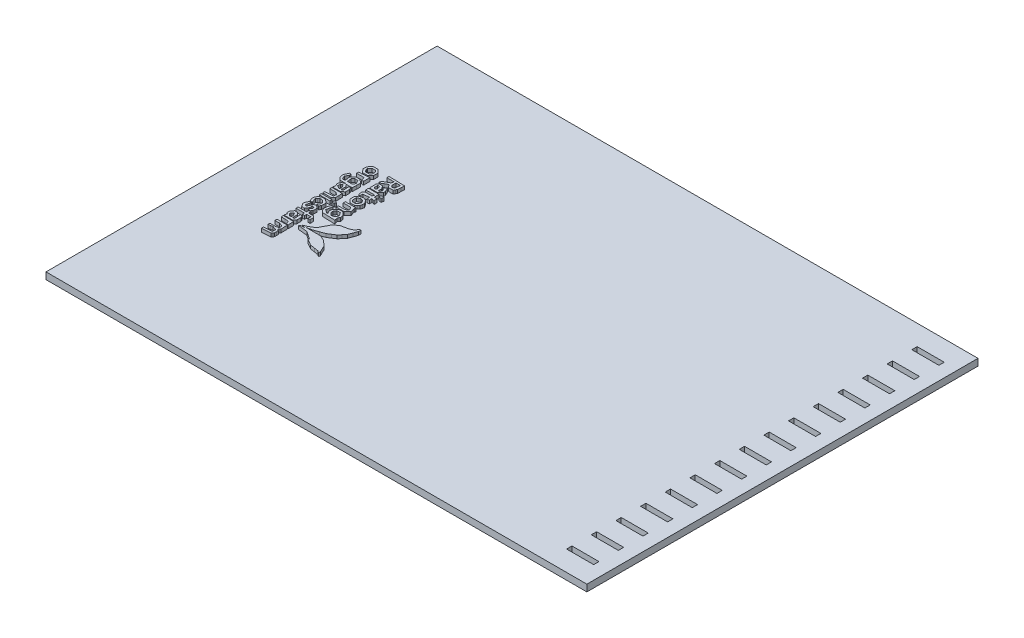
SolidWorks part; units mm, degrees
material "ABS"
ref_plane "Front Plane" through (0, 0, 0) normal (0, 0, 1) x (1, 0, 0)
ref_plane "Top Plane" through (0, 0, 0) normal (0, 1, 0) x (1, 0, 0)
ref_plane "Right Plane" through (0, 0, 0) normal (1, 0, 0) x (0, 0, -1)
sketch "Sketch1" plane through (0, 0, 0) normal (0, 1, 0) x (1, 0, 0)
  line L1 (-66.3921, 26.4776) -> (136.8079, 26.4776)
  line L2 (-66.3921, 26.4776) -> (-66.3921, -120.4614)
  line L3 (-66.3921, -120.4614) -> (136.8079, -120.4614)
  line L4 (136.8079, 26.4776) -> (136.8079, -120.4614)
  dimension "D1" = 203.2
  dimension "D2" = 146.939
extrude "Boss-Extrude1" add sketch "Sketch1" along normal blind 2.54
sketch "Sketch2" plane through (0, 2.54, 0) normal (0, 1, 0) x (0, 0, -1)
  line L14 (-120.4614, 66.3921) -> (-120.4614, -136.8079) construction
  line L15 (-110.8414, -131.7279) -> (-112.8414, -131.7279)
  line L16 (-110.8414, -131.7279) -> (-110.8414, -121.5679)
  line L17 (-110.8414, -121.5679) -> (-112.8414, -121.5679)
  line L18 (-112.8414, -131.7279) -> (-112.8414, -121.5679)
  line L19 (-120.4614, -136.8079) -> (26.4776, -136.8079) construction
  dimension "D1" = 2
  dimension "D2" = 7.62
  dimension "D3" = 5.08
  dimension "D4" = 10.16
extrude "Cut-Extrude1" cut sketch "Sketch2" against normal blind 2.794
pattern_linear "LPattern1" count 15 spacing 9.2642 along (0, 0, -1) of "Cut-Extrude1"
sketch "Sketch6" plane through (0, 2.54, 0) normal (0, 1, 0) x (1, 0, 0)
  line L8 (-40.8388, -35.001) -> (-40.6941, -35.6624)
  line L9 (-40.6941, -35.6624) -> (-40.2044, -36.1615)
  line L10 (-40.2044, -36.1615) -> (-39.7146, -36.6606)
  line L11 (-39.7146, -36.6606) -> (-38.5681, -36.6606)
  line L12 (-38.5681, -36.6606) -> (-37.4215, -36.6606)
  line L13 (-37.4215, -36.6606) -> (-37.9989, -36.8742)
  line L14 (-37.9989, -36.8742) -> (-38.5762, -37.0878)
  line L15 (-38.5762, -37.0878) -> (-38.8728, -37.6419)
  line L16 (-38.8728, -37.6419) -> (-39.1693, -38.1959)
  line L17 (-39.1693, -38.1959) -> (-38.9717, -38.7813)
  line L18 (-38.9717, -38.7813) -> (-38.774, -39.3666)
  line L19 (-38.774, -39.3666) -> (-38.8413, -39.8296)
  line L20 (-38.8413, -39.8296) -> (-38.9087, -40.2926)
  line L21 (-38.9087, -40.2926) -> (-37.4957, -40.2926)
  line L22 (-37.4957, -40.2926) -> (-36.0827, -40.2926)
  line L23 (-36.0827, -40.2926) -> (-35.4947, -39.8807)
  line L24 (-35.4947, -39.8807) -> (-34.9067, -39.4689)
  line L25 (-34.9067, -39.4689) -> (-34.9067, -38.7118)
  line L26 (-34.9067, -38.7118) -> (-34.9067, -37.9547)
  line L27 (-34.9067, -37.9547) -> (-35.0673, -37.5362)
  line L28 (-35.0673, -37.5362) -> (-35.2279, -37.1176)
  line L29 (-35.2279, -37.1176) -> (-35.5804, -37.1176)
  line L30 (-35.5804, -37.1176) -> (-35.9329, -37.1176)
  line L31 (-35.9329, -37.1176) -> (-35.8828, -38.2136)
  line L32 (-35.8828, -38.2136) -> (-35.8327, -39.3097)
  line L33 (-35.8327, -39.3097) -> (-36.1634, -39.4263)
  line L34 (-36.1634, -39.4263) -> (-36.4942, -39.543)
  line L35 (-36.4942, -39.543) -> (-36.4942, -38.6138)
  line L36 (-36.4942, -38.6138) -> (-36.4942, -37.6846)
  line L37 (-36.4942, -37.6846) -> (-36.9099, -37.2688)
  line L38 (-36.9099, -37.2688) -> (-37.3257, -36.853)
  line L39 (-37.3257, -36.853) -> (-36.1446, -36.853)
  line L40 (-36.1446, -36.853) -> (-34.9635, -36.853)
  line L41 (-34.9635, -36.853) -> (-34.9414, -35.2798)
  line L42 (-34.9414, -35.2798) -> (-34.9193, -33.7065)
  line L43 (-34.9193, -33.7065) -> (-35.6101, -33.1631)
  line L44 (-35.6101, -33.1631) -> (-36.301, -32.6197)
  line L45 (-36.301, -32.6197) -> (-37.0129, -32.6197)
  line L46 (-37.0129, -32.6197) -> (-37.7249, -32.6197)
  line L47 (-37.7249, -32.6197) -> (-38.331, -33.2649)
  line L48 (-38.331, -33.2649) -> (-38.9371, -33.9101)
  line L49 (-38.9371, -33.9101) -> (-38.8271, -34.8524)
  line L50 (-38.8271, -34.8524) -> (-38.7171, -35.7947)
  line L51 (-38.7171, -35.7947) -> (-39.1988, -35.7947)
  line L52 (-39.1988, -35.7947) -> (-39.6805, -35.7947)
  line L53 (-39.6805, -35.7947) -> (-39.977, -35.1441)
  line L54 (-39.977, -35.1441) -> (-40.2734, -34.4935)
  line L55 (-40.2734, -34.4935) -> (-39.8801, -33.8873)
  line L56 (-39.8801, -33.8873) -> (-39.4868, -33.2812)
  line L57 (-39.4868, -33.2812) -> (-39.6, -32.9504)
  line L58 (-39.6, -32.9504) -> (-39.7133, -32.6197)
  line L59 (-39.7133, -32.6197) -> (-39.9686, -32.6197)
  line L60 (-39.9686, -32.6197) -> (-40.2239, -32.6197)
  line L61 (-40.2239, -32.6197) -> (-40.6036, -33.4796)
  line L62 (-40.6036, -33.4796) -> (-40.9834, -34.3395)
  line L63 (-40.9834, -34.3395) -> (-40.8388, -35.001)
  line L64 (-38.3463, -38.4468) -> (-38.3463, -37.9426)
  line L65 (-38.3463, -37.9426) -> (-38.0415, -37.7543)
  line L66 (-38.0415, -37.7543) -> (-37.7368, -37.5659)
  line L67 (-37.7368, -37.5659) -> (-37.3801, -38.0538)
  line L68 (-37.3801, -38.0538) -> (-37.0233, -38.5417)
  line L69 (-37.0233, -38.5417) -> (-37.0233, -39.0203)
  line L70 (-37.0233, -39.0203) -> (-37.0233, -39.4989)
  line L71 (-37.0233, -39.4989) -> (-37.173, -39.4989)
  line L72 (-37.173, -39.4989) -> (-37.3227, -39.4989)
  line L73 (-37.3227, -39.4989) -> (-37.8345, -39.225)
  line L74 (-37.8345, -39.225) -> (-38.3463, -38.9511)
  line L75 (-38.3463, -38.9511) -> (-38.3463, -38.4468)
  line L76 (-38.0274, -34.8674) -> (-38.1055, -34.0723)
  line L77 (-38.1055, -34.0723) -> (-37.7761, -33.7429)
  line L78 (-37.7761, -33.7429) -> (-37.4467, -33.4135)
  line L79 (-37.4467, -33.4135) -> (-36.8324, -33.4135)
  line L80 (-36.8324, -33.4135) -> (-36.2183, -33.4135)
  line L81 (-36.2183, -33.4135) -> (-35.9075, -34.0955)
  line L82 (-35.9075, -34.0955) -> (-35.5968, -34.7775)
  line L83 (-35.5968, -34.7775) -> (-35.8759, -35.22)
  line L84 (-35.8759, -35.22) -> (-36.155, -35.6624)
  line L85 (-36.155, -35.6624) -> (-37.0522, -35.6624)
  line L86 (-37.0522, -35.6624) -> (-37.9494, -35.6624)
  line L87 (-37.9494, -35.6624) -> (-38.0274, -34.8674)
  line L88 (-39.1191, -28.1522) -> (-39.14, -28.5796)
  line L89 (-39.14, -28.5796) -> (-38.5916, -29.2767)
  line L90 (-38.5916, -29.2767) -> (-38.0433, -29.9739)
  line L91 (-38.0433, -29.9739) -> (-37.0041, -29.9739)
  line L92 (-37.0041, -29.9739) -> (-35.965, -29.9739)
  line L93 (-35.965, -29.9739) -> (-35.4358, -29.4447)
  line L94 (-35.4358, -29.4447) -> (-34.9067, -28.9155)
  line L95 (-34.9067, -28.9155) -> (-34.9067, -28.0727)
  line L96 (-34.9067, -28.0727) -> (-34.9067, -27.2298)
  line L97 (-34.9067, -27.2298) -> (-35.482, -26.6175)
  line L98 (-35.482, -26.6175) -> (-36.0572, -26.0051)
  line L99 (-36.0572, -26.0051) -> (-37.0285, -26.0051)
  line L100 (-37.0285, -26.0051) -> (-37.9997, -26.0051)
  line L101 (-37.9997, -26.0051) -> (-38.403, -26.4682)
  line L102 (-38.403, -26.4682) -> (-38.8064, -26.9312)
  line L103 (-38.8064, -26.9312) -> (-38.9523, -27.328)
  line L104 (-38.9523, -27.328) -> (-39.0982, -27.7249)
  line L105 (-39.0982, -27.7249) -> (-39.1191, -28.1522)
  line L106 (-38.3463, -27.8935) -> (-38.3463, -27.6304)
  line L107 (-38.3463, -27.6304) -> (-37.9305, -27.2147)
  line L108 (-37.9305, -27.2147) -> (-37.5147, -26.7989)
  line L109 (-37.5147, -26.7989) -> (-36.9251, -26.7989)
  line L110 (-36.9251, -26.7989) -> (-36.3354, -26.7989)
  line L111 (-36.3354, -26.7989) -> (-36.0179, -27.1164)
  line L112 (-36.0179, -27.1164) -> (-35.7004, -27.4339)
  line L113 (-35.7004, -27.4339) -> (-35.7004, -27.9895)
  line L114 (-35.7004, -27.9895) -> (-35.7004, -28.5451)
  line L115 (-35.7004, -28.5451) -> (-36.0179, -28.8626)
  line L116 (-36.0179, -28.8626) -> (-36.3354, -29.1801)
  line L117 (-36.3354, -29.1801) -> (-37.0669, -29.1801)
  line L118 (-37.0669, -29.1801) -> (-37.7985, -29.1801)
  line L119 (-37.7985, -29.1801) -> (-38.0724, -28.6684)
  line L120 (-38.0724, -28.6684) -> (-38.3463, -28.1566)
  line L121 (-38.3463, -28.1566) -> (-38.3463, -27.8935)
  line L122 (-39.1232, -47.6522) -> (-39.14, -48.0003)
  line L123 (-39.14, -48.0003) -> (-38.8661, -48.5121)
  line L124 (-38.8661, -48.5121) -> (-38.5922, -49.0239)
  line L125 (-38.5922, -49.0239) -> (-38.1764, -49.0239)
  line L126 (-38.1764, -49.0239) -> (-37.7605, -49.0239)
  line L127 (-37.7605, -49.0239) -> (-37.9511, -48.5609)
  line L128 (-37.9511, -48.5609) -> (-38.1417, -48.0978)
  line L129 (-38.1417, -48.0978) -> (-38.2645, -47.6743)
  line L130 (-38.2645, -47.6743) -> (-38.3873, -47.2507)
  line L131 (-38.3873, -47.2507) -> (-37.951, -46.8144)
  line L132 (-37.951, -46.8144) -> (-37.5147, -46.378)
  line L133 (-37.5147, -46.378) -> (-37.0233, -46.378)
  line L134 (-37.0233, -46.378) -> (-36.532, -46.378)
  line L135 (-36.532, -46.378) -> (-36.1162, -46.7938)
  line L136 (-36.1162, -46.7938) -> (-35.7004, -47.2096)
  line L137 (-35.7004, -47.2096) -> (-35.7004, -47.6669)
  line L138 (-35.7004, -47.6669) -> (-35.7004, -48.1243)
  line L139 (-35.7004, -48.1243) -> (-36.0093, -48.4331)
  line L140 (-36.0093, -48.4331) -> (-36.3181, -48.7419)
  line L141 (-36.3181, -48.7419) -> (-35.8503, -48.9215)
  line L142 (-35.8503, -48.9215) -> (-35.3824, -49.101)
  line L143 (-35.3824, -49.101) -> (-35.1486, -48.7317)
  line L144 (-35.1486, -48.7317) -> (-34.9148, -48.3624)
  line L145 (-34.9148, -48.3624) -> (-34.9107, -47.5217)
  line L146 (-34.9107, -47.5217) -> (-34.9067, -46.681)
  line L147 (-34.9067, -46.681) -> (-35.6038, -46.1327)
  line L148 (-35.6038, -46.1327) -> (-36.301, -45.5843)
  line L149 (-36.301, -45.5843) -> (-36.9441, -45.5843)
  line L150 (-36.9441, -45.5843) -> (-37.5873, -45.5843)
  line L151 (-37.5873, -45.5843) -> (-38.114, -45.8662)
  line L152 (-38.114, -45.8662) -> (-38.6407, -46.148)
  line L153 (-38.6407, -46.148) -> (-38.8736, -46.7261)
  line L154 (-38.8736, -46.7261) -> (-39.1065, -47.3041)
  line L155 (-39.1065, -47.3041) -> (-39.1232, -47.6522)
  line L156 (-39.1221, -50.8832) -> (-39.1401, -51.2874)
  line L157 (-39.1401, -51.2874) -> (-38.7282, -51.8754)
  line L158 (-38.7282, -51.8754) -> (-38.3162, -52.4635)
  line L159 (-38.3162, -52.4635) -> (-37.8171, -52.4635)
  line L160 (-37.8171, -52.4635) -> (-37.3179, -52.4635)
  line L161 (-37.3179, -52.4635) -> (-36.9061, -51.8754)
  line L162 (-36.9061, -51.8754) -> (-36.4942, -51.2874)
  line L163 (-36.4942, -51.2874) -> (-36.4942, -50.8171)
  line L164 (-36.4942, -50.8171) -> (-36.4942, -50.3468)
  line L165 (-36.4942, -50.3468) -> (-36.0973, -50.3468)
  line L166 (-36.0973, -50.3468) -> (-35.7004, -50.3468)
  line L167 (-35.7004, -50.3468) -> (-35.7004, -50.728)
  line L168 (-35.7004, -50.728) -> (-35.7004, -51.1093)
  line L169 (-35.7004, -51.1093) -> (-35.965, -51.2728)
  line L170 (-35.965, -51.2728) -> (-36.2296, -51.4364)
  line L171 (-36.2296, -51.4364) -> (-36.2296, -51.6936)
  line L172 (-36.2296, -51.6936) -> (-36.2296, -51.9509)
  line L173 (-36.2296, -51.9509) -> (-35.806, -52.1134)
  line L174 (-35.806, -52.1134) -> (-35.3824, -52.276)
  line L175 (-35.3824, -52.276) -> (-35.1486, -51.9067)
  line L176 (-35.1486, -51.9067) -> (-34.9148, -51.5374)
  line L177 (-34.9148, -51.5374) -> (-34.9107, -50.8508)
  line L178 (-34.9107, -50.8508) -> (-34.9067, -50.1642)
  line L179 (-34.9067, -50.1642) -> (-35.426, -49.6942)
  line L180 (-35.426, -49.6942) -> (-35.9453, -49.2243)
  line L181 (-35.9453, -49.2243) -> (-36.364, -49.3849)
  line L182 (-36.364, -49.3849) -> (-36.7827, -49.5456)
  line L183 (-36.7827, -49.5456) -> (-37.1788, -50.4937)
  line L184 (-37.1788, -50.4937) -> (-37.5749, -51.4418)
  line L185 (-37.5749, -51.4418) -> (-37.8944, -51.3288)
  line L186 (-37.8944, -51.3288) -> (-38.214, -51.2159)
  line L187 (-38.214, -51.2159) -> (-38.1648, -50.8475)
  line L188 (-38.1648, -50.8475) -> (-38.1156, -50.4791)
  line L189 (-38.1156, -50.4791) -> (-37.9355, -49.8838)
  line L190 (-37.9355, -49.8838) -> (-37.7554, -49.2885)
  line L191 (-37.7554, -49.2885) -> (-38.1427, -49.2885)
  line L192 (-38.1427, -49.2885) -> (-38.53, -49.2885)
  line L193 (-38.53, -49.2885) -> (-38.8171, -49.8838)
  line L194 (-38.8171, -49.8838) -> (-39.1042, -50.4791)
  line L195 (-39.1042, -50.4791) -> (-39.1221, -50.8832)
  line L196 (-39.1401, -56.7401) -> (-39.1401, -57.1947)
  line L197 (-39.1401, -57.1947) -> (-38.9003, -57.3429)
  line L198 (-38.9003, -57.3429) -> (-38.6606, -57.4911)
  line L199 (-38.6606, -57.4911) -> (-38.7989, -58.02)
  line L200 (-38.7989, -58.02) -> (-38.9372, -58.5489)
  line L201 (-38.9372, -58.5489) -> (-37.3378, -58.5489)
  line L202 (-37.3378, -58.5489) -> (-35.7383, -58.5489)
  line L203 (-35.7383, -58.5489) -> (-35.3225, -58.1331)
  line L204 (-35.3225, -58.1331) -> (-34.9067, -57.7173)
  line L205 (-34.9067, -57.7173) -> (-34.9067, -56.9641)
  line L206 (-34.9067, -56.9641) -> (-34.9067, -56.2109)
  line L207 (-34.9067, -56.2109) -> (-35.0674, -55.7924)
  line L208 (-35.0674, -55.7924) -> (-35.228, -55.3739)
  line L209 (-35.228, -55.3739) -> (-35.6013, -55.3739)
  line L210 (-35.6013, -55.3739) -> (-35.9747, -55.3739)
  line L211 (-35.9747, -55.3739) -> (-35.9037, -56.4698)
  line L212 (-35.9037, -56.4698) -> (-35.8328, -57.5658)
  line L213 (-35.8328, -57.5658) -> (-36.1635, -57.6825)
  line L214 (-36.1635, -57.6825) -> (-36.4942, -57.7992)
  line L215 (-36.4942, -57.7992) -> (-36.4942, -56.87)
  line L216 (-36.4942, -56.87) -> (-36.4942, -55.9408)
  line L217 (-36.4942, -55.9408) -> (-36.91, -55.5251)
  line L218 (-36.91, -55.5251) -> (-37.3258, -55.1093)
  line L219 (-37.3258, -55.1093) -> (-37.8211, -55.1093)
  line L220 (-37.8211, -55.1093) -> (-38.3163, -55.1093)
  line L221 (-38.3163, -55.1093) -> (-38.7282, -55.6973)
  line L222 (-38.7282, -55.6973) -> (-39.1401, -56.2854)
  line L223 (-39.1401, -56.2854) -> (-39.1401, -56.7401)
  line L224 (-38.3463, -56.8086) -> (-38.3463, -56.497)
  line L225 (-38.3463, -56.497) -> (-37.9679, -56.183)
  line L226 (-37.9679, -56.183) -> (-37.5895, -55.8689)
  line L227 (-37.5895, -55.8689) -> (-37.3065, -56.3977)
  line L228 (-37.3065, -56.3977) -> (-37.0234, -56.9266)
  line L229 (-37.0234, -56.9266) -> (-37.0234, -57.3409)
  line L230 (-37.0234, -57.3409) -> (-37.0234, -57.7551)
  line L231 (-37.0234, -57.7551) -> (-37.3674, -57.7551)
  line L232 (-37.3674, -57.7551) -> (-37.7113, -57.7551)
  line L233 (-37.7113, -57.7551) -> (-38.0288, -57.4376)
  line L234 (-38.0288, -57.4376) -> (-38.3463, -57.1201)
  line L235 (-38.3463, -57.1201) -> (-38.3463, -56.8086)
  line L236 (-38.8754, -30.8999) -> (-38.8754, -31.2968)
  line L237 (-38.8754, -31.2968) -> (-37.4253, -31.2968)
  line L238 (-37.4253, -31.2968) -> (-35.9751, -31.2968)
  line L239 (-35.9751, -31.2968) -> (-35.8091, -31.9583)
  line L240 (-35.8091, -31.9583) -> (-35.643, -32.6197)
  line L241 (-35.643, -32.6197) -> (-35.2845, -32.6197)
  line L242 (-35.2845, -32.6197) -> (-34.926, -32.6197)
  line L243 (-34.926, -32.6197) -> (-34.9505, -31.3963)
  line L244 (-34.9505, -31.3963) -> (-34.9751, -30.1728)
  line L245 (-34.9751, -30.1728) -> (-36.3299, -30.3357)
  line L246 (-36.3299, -30.3357) -> (-37.6848, -30.4984)
  line L247 (-37.6848, -30.4984) -> (-38.2801, -30.5008)
  line L248 (-38.2801, -30.5008) -> (-38.8754, -30.503)
  line L249 (-38.8754, -30.503) -> (-38.8754, -30.8999)
  line L250 (-38.8754, -40.9541) -> (-38.8754, -41.351)
  line L251 (-38.8754, -41.351) -> (-37.7354, -41.351)
  line L252 (-37.7354, -41.351) -> (-36.5953, -41.351)
  line L253 (-36.5953, -41.351) -> (-36.1191, -41.6992)
  line L254 (-36.1191, -41.6992) -> (-35.6429, -42.0474)
  line L255 (-35.6429, -42.0474) -> (-35.7404, -42.5591)
  line L256 (-35.7404, -42.5591) -> (-35.8379, -43.0708)
  line L257 (-35.8379, -43.0708) -> (-37.3566, -43.1501)
  line L258 (-37.3566, -43.1501) -> (-38.8754, -43.2295)
  line L259 (-38.8754, -43.2295) -> (-38.8754, -43.6131)
  line L260 (-38.8754, -43.6131) -> (-38.8754, -43.9968)
  line L261 (-38.8754, -43.9968) -> (-37.3068, -43.9968)
  line L262 (-37.3068, -43.9968) -> (-35.7382, -43.9968)
  line L263 (-35.7382, -43.9968) -> (-35.3275, -43.5861)
  line L264 (-35.3275, -43.5861) -> (-34.9168, -43.1754)
  line L265 (-34.9168, -43.1754) -> (-34.9463, -41.8663)
  line L266 (-34.9463, -41.8663) -> (-34.9758, -40.5572)
  line L267 (-34.9758, -40.5572) -> (-36.9256, -40.5572)
  line L268 (-36.9256, -40.5572) -> (-38.8754, -40.5572)
  line L269 (-38.8754, -40.5572) -> (-38.8754, -40.9541)
  line L270 (-38.8754, -44.9228) -> (-38.8754, -45.3197)
  line L271 (-38.8754, -45.3197) -> (-36.891, -45.3197)
  line L272 (-36.891, -45.3197) -> (-34.9067, -45.3197)
  line L273 (-34.9067, -45.3197) -> (-34.9067, -44.9228)
  line L274 (-34.9067, -44.9228) -> (-34.9067, -44.526)
  line L275 (-34.9067, -44.526) -> (-36.891, -44.526)
  line L276 (-36.891, -44.526) -> (-38.8754, -44.526)
  line L277 (-38.8754, -44.526) -> (-38.8754, -44.9228)
  line L278 (-38.8754, -53.6541) -> (-38.8754, -54.051)
  line L279 (-38.8754, -54.051) -> (-37.2879, -54.051)
  line L280 (-37.2879, -54.051) -> (-35.7004, -54.051)
  line L281 (-35.7004, -54.051) -> (-35.7004, -54.4478)
  line L282 (-35.7004, -54.4478) -> (-35.7004, -54.8447)
  line L283 (-35.7004, -54.8447) -> (-35.3035, -54.8447)
  line L284 (-35.3035, -54.8447) -> (-34.9067, -54.8447)
  line L285 (-34.9067, -54.8447) -> (-34.9067, -54.4478)
  line L286 (-34.9067, -54.4478) -> (-34.9067, -54.051)
  line L287 (-34.9067, -54.051) -> (-34.1129, -54.051)
  line L288 (-34.1129, -54.051) -> (-33.3192, -54.051)
  line L289 (-33.3192, -54.051) -> (-33.3192, -54.5801)
  line L290 (-33.3192, -54.5801) -> (-33.3192, -55.1093)
  line L291 (-33.3192, -55.1093) -> (-32.9223, -55.1093)
  line L292 (-32.9223, -55.1093) -> (-32.5254, -55.1093)
  line L293 (-32.5254, -55.1093) -> (-32.5254, -54.5008)
  line L294 (-32.5254, -54.5008) -> (-32.5254, -53.8922)
  line L295 (-32.5254, -53.8922) -> (-32.8429, -53.5747)
  line L296 (-32.8429, -53.5747) -> (-33.1604, -53.2572)
  line L297 (-33.1604, -53.2572) -> (-34.0335, -53.2572)
  line L298 (-34.0335, -53.2572) -> (-34.9067, -53.2572)
  line L299 (-34.9067, -53.2572) -> (-34.9067, -52.8603)
  line L300 (-34.9067, -52.8603) -> (-34.9067, -52.4635)
  line L301 (-34.9067, -52.4635) -> (-35.3035, -52.4635)
  line L302 (-35.3035, -52.4635) -> (-35.7004, -52.4635)
  line L303 (-35.7004, -52.4635) -> (-35.7004, -52.8603)
  line L304 (-35.7004, -52.8603) -> (-35.7004, -53.2572)
  line L305 (-35.7004, -53.2572) -> (-37.2879, -53.2572)
  line L306 (-37.2879, -53.2572) -> (-38.8754, -53.2572)
  line L307 (-38.8754, -53.2572) -> (-38.8754, -53.6541)
  line L308 (-38.8754, -59.1965) -> (-38.8754, -59.5796)
  line L309 (-38.8754, -59.5796) -> (-37.4863, -59.6595)
  line L310 (-37.4863, -59.6595) -> (-36.0973, -59.7395)
  line L311 (-36.0973, -59.7395) -> (-35.8361, -60.3348)
  line L312 (-35.8361, -60.3348) -> (-35.5749, -60.9301)
  line L313 (-35.5749, -60.9301) -> (-35.2574, -60.9301)
  line L314 (-35.2574, -60.9301) -> (-34.9398, -60.9301)
  line L315 (-34.9398, -60.9301) -> (-34.9544, -59.8718)
  line L316 (-34.9544, -59.8718) -> (-34.9691, -58.8135)
  line L317 (-34.9691, -58.8135) -> (-36.9222, -58.8135)
  line L318 (-36.9222, -58.8135) -> (-38.8754, -58.8135)
  line L319 (-38.8754, -58.8135) -> (-38.8754, -59.1965)
  line L320 (-38.8754, -61.5916) -> (-38.8754, -61.9885)
  line L321 (-38.8754, -61.9885) -> (-37.9666, -61.9885)
  line L322 (-37.9666, -61.9885) -> (-37.0578, -61.9885)
  line L323 (-37.0578, -61.9885) -> (-36.3791, -62.2465)
  line L324 (-36.3791, -62.2465) -> (-35.7004, -62.5045)
  line L325 (-35.7004, -62.5045) -> (-35.7004, -63.0094)
  line L326 (-35.7004, -63.0094) -> (-35.7004, -63.5143)
  line L327 (-35.7004, -63.5143) -> (-36.2957, -63.6738)
  line L328 (-36.2957, -63.6738) -> (-36.891, -63.8333)
  line L329 (-36.891, -63.8333) -> (-37.8832, -63.8369)
  line L330 (-37.8832, -63.8369) -> (-38.8754, -63.8406)
  line L331 (-38.8754, -63.8406) -> (-38.8754, -64.2208)
  line L332 (-38.8754, -64.2208) -> (-38.8754, -64.601)
  line L333 (-38.8754, -64.601) -> (-38.0155, -64.464)
  line L334 (-38.0155, -64.464) -> (-37.1556, -64.327)
  line L335 (-37.1556, -64.327) -> (-36.4097, -64.6134)
  line L336 (-36.4097, -64.6134) -> (-35.6637, -64.8997)
  line L337 (-35.6637, -64.8997) -> (-35.7482, -65.4946)
  line L338 (-35.7482, -65.4946) -> (-35.8327, -66.0895)
  line L339 (-35.8327, -66.0895) -> (-37.3541, -66.1689)
  line L340 (-37.3541, -66.1689) -> (-38.8754, -66.2482)
  line L341 (-38.8754, -66.2482) -> (-38.8754, -66.6627)
  line L342 (-38.8754, -66.6627) -> (-38.8754, -67.0772)
  line L343 (-38.8754, -67.0772) -> (-38.3374, -67.043)
  line L344 (-38.3374, -67.043) -> (-35.3996, -66.8559)
  line L345 (-35.3996, -66.8559) -> (-35.1572, -66.4727)
  line L346 (-35.1572, -66.4727) -> (-34.9148, -66.0895)
  line L347 (-34.9148, -66.0895) -> (-34.9107, -65.3775)
  line L348 (-34.9107, -65.3775) -> (-34.9067, -64.6655)
  line L349 (-34.9067, -64.6655) -> (-35.1841, -64.4941)
  line L350 (-35.1841, -64.4941) -> (-35.4615, -64.3226)
  line L351 (-35.4615, -64.3226) -> (-35.1928, -63.9988)
  line L352 (-35.1928, -63.9988) -> (-34.924, -63.6749)
  line L353 (-34.924, -63.6749) -> (-34.9489, -62.4348)
  line L354 (-34.9489, -62.4348) -> (-34.9738, -61.1947)
  line L355 (-34.9738, -61.1947) -> (-36.9246, -61.1947)
  line L356 (-36.9246, -61.1947) -> (-38.8754, -61.1947)
  line L357 (-38.8754, -61.1947) -> (-38.8754, -61.5916)
  line L358 (-34.1129, -44.9384) -> (-34.1129, -45.3197)
  line L359 (-34.1129, -45.3197) -> (-33.7317, -45.3197)
  line L360 (-33.7317, -45.3197) -> (-33.3504, -45.3197)
  line L361 (-33.3504, -45.3197) -> (-33.1686, -45.0255)
  line L362 (-33.1686, -45.0255) -> (-32.9868, -44.7314)
  line L363 (-32.9868, -44.7314) -> (-33.3388, -44.5138)
  line L364 (-33.3388, -44.5138) -> (-33.6908, -44.2963)
  line L365 (-33.6908, -44.2963) -> (-33.9018, -44.4267)
  line L366 (-33.9018, -44.4267) -> (-34.1129, -44.5572)
  line L367 (-34.1129, -44.5572) -> (-34.1129, -44.9384)
  line L368 (-33.5659, -48.3992) -> (-33.5838, -49.2298)
  line L369 (-33.5838, -49.2298) -> (-33.0782, -49.8545)
  line L370 (-33.0782, -49.8545) -> (-32.5725, -50.4791)
  line L371 (-32.5725, -50.4791) -> (-30.1296, -50.573)
  line L372 (-30.1296, -50.573) -> (-27.6867, -50.6669)
  line L373 (-27.6867, -50.6669) -> (-27.846, -50.0576)
  line L374 (-27.846, -50.0576) -> (-28.0054, -49.4483)
  line L375 (-28.0054, -49.4483) -> (-27.7223, -49.1072)
  line L376 (-27.7223, -49.1072) -> (-27.4392, -48.7662)
  line L377 (-27.4392, -48.7662) -> (-27.6043, -48.1086)
  line L378 (-27.6043, -48.1086) -> (-27.7693, -47.451)
  line L379 (-27.7693, -47.451) -> (-28.3452, -46.9145)
  line L380 (-28.3452, -46.9145) -> (-28.921, -46.378)
  line L381 (-28.921, -46.378) -> (-29.6769, -46.378)
  line L382 (-29.6769, -46.378) -> (-30.4328, -46.378)
  line L383 (-30.4328, -46.378) -> (-31.0822, -47.0275)
  line L384 (-31.0822, -47.0275) -> (-31.7317, -47.6769)
  line L385 (-31.7317, -47.6769) -> (-31.7317, -48.2355)
  line L386 (-31.7317, -48.2355) -> (-31.7317, -48.7941)
  line L387 (-31.7317, -48.7941) -> (-31.4578, -49.3059)
  line L388 (-31.4578, -49.3059) -> (-31.1839, -49.8176)
  line L389 (-31.1839, -49.8176) -> (-31.3989, -49.8176)
  line L390 (-31.3989, -49.8176) -> (-31.6139, -49.8176)
  line L391 (-31.6139, -49.8176) -> (-32.2272, -49.3881)
  line L392 (-32.2272, -49.3881) -> (-32.8405, -48.9585)
  line L393 (-32.8405, -48.9585) -> (-32.7016, -48.2636)
  line L394 (-32.7016, -48.2636) -> (-32.5628, -47.5687)
  line L395 (-32.5628, -47.5687) -> (-32.478, -47.068)
  line L396 (-32.478, -47.068) -> (-32.3931, -46.5673)
  line L397 (-32.3931, -46.5673) -> (-32.6801, -46.4652)
  line L398 (-32.6801, -46.4652) -> (-32.9671, -46.3631)
  line L399 (-32.9671, -46.3631) -> (-33.2575, -46.9659)
  line L400 (-33.2575, -46.9659) -> (-33.5479, -47.5687)
  line L401 (-33.5479, -47.5687) -> (-33.5659, -48.3992)
  line L402 (-30.9299, -48.5198) -> (-30.9218, -48.0978)
  line L403 (-30.9218, -48.0978) -> (-30.6521, -47.6348)
  line L404 (-30.6521, -47.6348) -> (-30.3825, -47.1718)
  line L405 (-30.3825, -47.1718) -> (-29.7403, -47.1718)
  line L406 (-29.7403, -47.1718) -> (-29.098, -47.1718)
  line L407 (-29.098, -47.1718) -> (-28.6763, -47.8155)
  line L408 (-28.6763, -47.8155) -> (-28.2545, -48.4592)
  line L409 (-28.2545, -48.4592) -> (-28.5376, -48.9882)
  line L410 (-28.5376, -48.9882) -> (-28.8207, -49.5172)
  line L411 (-28.8207, -49.5172) -> (-29.3691, -49.6913)
  line L412 (-29.3691, -49.6913) -> (-29.9175, -49.8653)
  line L413 (-29.9175, -49.8653) -> (-30.4277, -49.4036)
  line L414 (-30.4277, -49.4036) -> (-30.9379, -48.9419)
  line L415 (-30.9379, -48.9419) -> (-30.9299, -48.5198)
  line L416 (-31.0663, -59.3896) -> (-29.2954, -59.5688)
  line L417 (-29.2954, -59.5688) -> (-27.8677, -60.5168)
  line L418 (-27.8677, -60.5168) -> (-26.44, -61.4647)
  line L419 (-26.44, -61.4647) -> (-26.44, -61.7154)
  line L420 (-26.44, -61.7154) -> (-26.44, -61.9662)
  line L421 (-26.44, -61.9662) -> (-25.3155, -62.6236)
  line L422 (-25.3155, -62.6236) -> (-24.191, -63.281)
  line L423 (-24.191, -63.281) -> (-22.5109, -63.5503)
  line L424 (-22.5109, -63.5503) -> (-20.8309, -63.8197)
  line L425 (-20.8309, -63.8197) -> (-20.4604, -64.1271)
  line L426 (-20.4604, -64.1271) -> (-20.09, -64.4345)
  line L427 (-20.09, -64.4345) -> (-20.0926, -64.0714)
  line L428 (-20.0926, -64.0714) -> (-20.0952, -63.7083)
  line L429 (-20.0952, -63.7083) -> (-20.7172, -62.3853)
  line L430 (-20.7172, -62.3853) -> (-21.3393, -61.0624)
  line L431 (-21.3393, -61.0624) -> (-22.3165, -60.183)
  line L432 (-22.3165, -60.183) -> (-23.2938, -59.3036)
  line L433 (-23.2938, -59.3036) -> (-24.2716, -58.8762)
  line L434 (-24.2716, -58.8762) -> (-25.2494, -58.4487)
  line L435 (-25.2494, -58.4487) -> (-27.9705, -58.4327)
  line L436 (-27.9705, -58.4327) -> (-30.6916, -58.4166)
  line L437 (-30.6916, -58.4166) -> (-29.703, -58.2111)
  line L438 (-29.703, -58.2111) -> (-28.7143, -58.0057)
  line L439 (-28.7143, -58.0057) -> (-26.8496, -57.3346)
  line L440 (-26.8496, -57.3346) -> (-24.9848, -56.6634)
  line L441 (-24.9848, -56.6634) -> (-23.7214, -55.8545)
  line L442 (-23.7214, -55.8545) -> (-22.458, -55.0456)
  line L443 (-22.458, -55.0456) -> (-21.5701, -54.0083)
  line L444 (-21.5701, -54.0083) -> (-20.6822, -52.971)
  line L445 (-20.6822, -52.971) -> (-20.1215, -51.4333)
  line L446 (-20.1215, -51.4333) -> (-19.5608, -49.8956)
  line L447 (-19.5608, -49.8956) -> (-19.5608, -49.4597)
  line L448 (-19.5608, -49.4597) -> (-19.5608, -49.0239)
  line L449 (-19.5608, -49.0239) -> (-19.8161, -49.0239)
  line L450 (-19.8161, -49.0239) -> (-20.0714, -49.0239)
  line L451 (-20.0714, -49.0239) -> (-20.3531, -49.5503)
  line L452 (-20.3531, -49.5503) -> (-20.6349, -50.0767)
  line L453 (-20.6349, -50.0767) -> (-21.4209, -50.4832)
  line L454 (-21.4209, -50.4832) -> (-22.207, -50.8897)
  line L455 (-22.207, -50.8897) -> (-23.5726, -51.1487)
  line L456 (-23.5726, -51.1487) -> (-24.9382, -51.4077)
  line L457 (-24.9382, -51.4077) -> (-25.8091, -52.072)
  line L458 (-25.8091, -52.072) -> (-26.68, -52.7362)
  line L459 (-26.68, -52.7362) -> (-27.6648, -54.6102)
  line L460 (-27.6648, -54.6102) -> (-28.6495, -56.4842)
  line L461 (-28.6495, -56.4842) -> (-29.6743, -57.1311)
  line L462 (-29.6743, -57.1311) -> (-30.6991, -57.778)
  line L463 (-30.6991, -57.778) -> (-31.4138, -58.0683)
  line L464 (-31.4138, -58.0683) -> (-32.1285, -58.3585)
  line L465 (-32.1285, -58.3585) -> (-31.4671, -58.5596)
  line L466 (-31.4671, -58.5596) -> (-30.8056, -58.7607)
  line L467 (-30.8056, -58.7607) -> (-31.6214, -58.7871)
  line L468 (-31.6214, -58.7871) -> (-32.4372, -58.8135)
  line L469 (-32.4372, -58.8135) -> (-32.6372, -59.0119)
  line L470 (-32.6372, -59.0119) -> (-32.8371, -59.2104)
  line L471 (-32.8371, -59.2104) -> (-31.0663, -59.3896)
  line L472 (-31.7317, -26.6579) -> (-31.7317, -27.0635)
  line L473 (-31.7317, -27.0635) -> (-30.3894, -27.0635)
  line L474 (-30.3894, -27.0635) -> (-29.047, -27.0635)
  line L475 (-29.047, -27.0635) -> (-29.1355, -27.5229)
  line L476 (-29.1355, -27.5229) -> (-29.224, -27.9824)
  line L477 (-29.224, -27.9824) -> (-30.3657, -28.6122)
  line L478 (-30.3657, -28.6122) -> (-31.5075, -29.242)
  line L479 (-31.5075, -29.242) -> (-31.6522, -29.6194)
  line L480 (-31.6522, -29.6194) -> (-31.7971, -29.9967)
  line L481 (-31.7971, -29.9967) -> (-31.6723, -30.1214)
  line L482 (-31.6723, -30.1214) -> (-31.5475, -30.2462)
  line L483 (-31.5475, -30.2462) -> (-30.2985, -29.5481)
  line L484 (-30.2985, -29.5481) -> (-29.0494, -28.8499)
  line L485 (-29.0494, -28.8499) -> (-28.6557, -29.4119)
  line L486 (-28.6557, -29.4119) -> (-28.2621, -29.9739)
  line L487 (-28.2621, -29.9739) -> (-27.3604, -29.9739)
  line L488 (-27.3604, -29.9739) -> (-26.4586, -29.9739)
  line L489 (-26.4586, -29.9739) -> (-26.1588, -29.4136)
  line L490 (-26.1588, -29.4136) -> (-25.8589, -28.8533)
  line L491 (-25.8589, -28.8533) -> (-25.8187, -27.6276)
  line L492 (-25.8187, -27.6276) -> (-25.7785, -26.402)
  line L493 (-25.7785, -26.402) -> (-28.7551, -26.3272)
  line L494 (-28.7551, -26.3272) -> (-31.7317, -26.2524)
  line L495 (-31.7317, -26.2524) -> (-31.7317, -26.6579)
  line L496 (-28.288, -27.7911) -> (-28.2921, -27.0635)
  line L497 (-28.2921, -27.0635) -> (-27.4824, -27.0635)
  line L498 (-27.4824, -27.0635) -> (-26.6727, -27.0635)
  line L499 (-26.6727, -27.0635) -> (-26.7548, -28.0534)
  line L500 (-26.7548, -28.0534) -> (-26.8369, -29.0434)
  line L501 (-26.8369, -29.0434) -> (-27.3343, -29.1378)
  line L502 (-27.3343, -29.1378) -> (-27.8318, -29.2322)
  line L503 (-27.8318, -29.2322) -> (-28.0579, -28.8754)
  line L504 (-28.0579, -28.8754) -> (-28.284, -28.5187)
  line L505 (-28.284, -28.5187) -> (-28.288, -27.7911)
  line L506 (-31.6913, -32.4022) -> (-31.6625, -33.678)
  line L507 (-31.6625, -33.678) -> (-30.1096, -33.678)
  line L508 (-30.1096, -33.678) -> (-28.5567, -33.678)
  line L509 (-28.5567, -33.678) -> (-28.0275, -33.1489)
  line L510 (-28.0275, -33.1489) -> (-27.4983, -32.6197)
  line L511 (-27.4983, -32.6197) -> (-27.4983, -32.2353)
  line L512 (-27.4983, -32.2353) -> (-27.4983, -31.8509)
  line L513 (-27.4983, -31.8509) -> (-27.8054, -31.177)
  line L514 (-27.8054, -31.177) -> (-28.1125, -30.503)
  line L515 (-28.1125, -30.503) -> (-28.319, -30.503)
  line L516 (-28.319, -30.503) -> (-28.5254, -30.503)
  line L517 (-28.5254, -30.503) -> (-28.6856, -30.7621)
  line L518 (-28.6856, -30.7621) -> (-28.8457, -31.0213)
  line L519 (-28.8457, -31.0213) -> (-28.5699, -31.5367)
  line L520 (-28.5699, -31.5367) -> (-28.294, -32.0522)
  line L521 (-28.294, -32.0522) -> (-28.4536, -32.4682)
  line L522 (-28.4536, -32.4682) -> (-28.6133, -32.8843)
  line L523 (-28.6133, -32.8843) -> (-28.8496, -32.8843)
  line L524 (-28.8496, -32.8843) -> (-29.0858, -32.8843)
  line L525 (-29.0858, -32.8843) -> (-29.0858, -32.2817)
  line L526 (-29.0858, -32.2817) -> (-29.0858, -31.6791)
  line L527 (-29.0858, -31.6791) -> (-29.4977, -31.0911)
  line L528 (-29.4977, -31.0911) -> (-29.9096, -30.503)
  line L529 (-29.9096, -30.503) -> (-30.5031, -30.503)
  line L530 (-30.5031, -30.503) -> (-31.0967, -30.503)
  line L531 (-31.0967, -30.503) -> (-31.4084, -30.8147)
  line L532 (-31.4084, -30.8147) -> (-31.72, -31.1264)
  line L533 (-31.72, -31.1264) -> (-31.6913, -32.4022)
  line L534 (-30.9379, -31.9666) -> (-30.9379, -31.2968)
  line L535 (-30.9379, -31.2968) -> (-30.5461, -31.2968)
  line L536 (-30.5461, -31.2968) -> (-30.1543, -31.2968)
  line L537 (-30.1543, -31.2968) -> (-29.9851, -31.9706)
  line L538 (-29.9851, -31.9706) -> (-29.816, -32.6444)
  line L539 (-29.816, -32.6444) -> (-29.9687, -32.797)
  line L540 (-29.9687, -32.797) -> (-30.1213, -32.9497)
  line L541 (-30.1213, -32.9497) -> (-30.5296, -32.793)
  line L542 (-30.5296, -32.793) -> (-30.9379, -32.6363)
  line L543 (-30.9379, -32.6363) -> (-30.9379, -31.9666)
  line L544 (-31.7317, -34.4718) -> (-31.7317, -35.001)
  line L545 (-31.7317, -35.001) -> (-30.0202, -35.001)
  line L546 (-30.0202, -35.001) -> (-28.3087, -35.001)
  line L547 (-28.3087, -35.001) -> (-28.461, -35.3978)
  line L548 (-28.461, -35.3978) -> (-28.6133, -35.7947)
  line L549 (-28.6133, -35.7947) -> (-29.8755, -35.7947)
  line L550 (-29.8755, -35.7947) -> (-31.1377, -35.7947)
  line L551 (-31.1377, -35.7947) -> (-31.455, -36.177)
  line L552 (-31.455, -36.177) -> (-31.7723, -36.5593)
  line L553 (-31.7723, -36.5593) -> (-31.6858, -37.1485)
  line L554 (-31.6858, -37.1485) -> (-31.5994, -37.7376)
  line L555 (-31.5994, -37.7376) -> (-31.2687, -37.8466)
  line L556 (-31.2687, -37.8466) -> (-30.9379, -37.9555)
  line L557 (-30.9379, -37.9555) -> (-30.9379, -37.4309)
  line L558 (-30.9379, -37.4309) -> (-30.9379, -36.9063)
  line L559 (-30.9379, -36.9063) -> (-29.7473, -36.8116)
  line L560 (-29.7473, -36.8116) -> (-28.5567, -36.717)
  line L561 (-28.5567, -36.717) -> (-28.5567, -37.1819)
  line L562 (-28.5567, -37.1819) -> (-28.5567, -37.6468)
  line L563 (-28.5567, -37.6468) -> (-28.1598, -37.6468)
  line L564 (-28.1598, -37.6468) -> (-27.7629, -37.6468)
  line L565 (-27.7629, -37.6468) -> (-27.7629, -37.1424)
  line L566 (-27.7629, -37.1424) -> (-27.7629, -36.638)
  line L567 (-27.7629, -36.638) -> (-27.2338, -36.7764)
  line L568 (-27.2338, -36.7764) -> (-26.7046, -36.9148)
  line L569 (-26.7046, -36.9148) -> (-26.7046, -36.3547)
  line L570 (-26.7046, -36.3547) -> (-26.7046, -35.7947)
  line L571 (-26.7046, -35.7947) -> (-27.2338, -35.7947)
  line L572 (-27.2338, -35.7947) -> (-27.7629, -35.7947)
  line L573 (-27.7629, -35.7947) -> (-27.7629, -34.8687)
  line L574 (-27.7629, -34.8687) -> (-27.7629, -33.9426)
  line L575 (-27.7629, -33.9426) -> (-29.7473, -33.9426)
  line L576 (-29.7473, -33.9426) -> (-31.7317, -33.9426)
  line L577 (-31.7317, -33.9426) -> (-31.7317, -34.4718)
  line L578 (-31.7317, -40.1277) -> (-31.7317, -40.92)
  line L579 (-31.7317, -40.92) -> (-31.1564, -41.5323)
  line L580 (-31.1564, -41.5323) -> (-30.5811, -42.1447)
  line L581 (-30.5811, -42.1447) -> (-29.7012, -42.1447)
  line L582 (-29.7012, -42.1447) -> (-28.8213, -42.1447)
  line L583 (-28.8213, -42.1447) -> (-28.2988, -41.6223)
  line L584 (-28.2988, -41.6223) -> (-27.7764, -41.0998)
  line L585 (-27.7764, -41.0998) -> (-27.6082, -40.4297)
  line L586 (-27.6082, -40.4297) -> (-27.44, -39.7596)
  line L587 (-27.44, -39.7596) -> (-27.8799, -39.0883)
  line L588 (-27.8799, -39.0883) -> (-28.3198, -38.4169)
  line L589 (-28.3198, -38.4169) -> (-28.9674, -38.1707)
  line L590 (-28.9674, -38.1707) -> (-29.615, -37.9245)
  line L591 (-29.615, -37.9245) -> (-30.3426, -38.1944)
  line L592 (-30.3426, -38.1944) -> (-31.0702, -38.4644)
  line L593 (-31.0702, -38.4644) -> (-31.4009, -38.8999)
  line L594 (-31.4009, -38.8999) -> (-31.7317, -39.3354)
  line L595 (-31.7317, -39.3354) -> (-31.7317, -40.1277)
  line L596 (-30.9379, -39.9666) -> (-30.9379, -39.2173)
  line L597 (-30.9379, -39.2173) -> (-30.3525, -39.0007)
  line L598 (-30.3525, -39.0007) -> (-29.767, -38.7841)
  line L599 (-29.767, -38.7841) -> (-29.2858, -38.91)
  line L600 (-29.2858, -38.91) -> (-28.8045, -39.0358)
  line L601 (-28.8045, -39.0358) -> (-28.5295, -39.5497)
  line L602 (-28.5295, -39.5497) -> (-28.2545, -40.0635)
  line L603 (-28.2545, -40.0635) -> (-28.6763, -40.7072)
  line L604 (-28.6763, -40.7072) -> (-29.098, -41.351)
  line L605 (-29.098, -41.351) -> (-29.7005, -41.351)
  line L606 (-29.7005, -41.351) -> (-30.3029, -41.351)
  line L607 (-30.3029, -41.351) -> (-30.6204, -41.0335)
  line L608 (-30.6204, -41.0335) -> (-30.9379, -40.716)
  line L609 (-30.9379, -40.716) -> (-30.9379, -39.9666)
  line L610 (-31.7317, -43.0708) -> (-31.7317, -43.4676)
  line L611 (-31.7317, -43.4676) -> (-30.2858, -43.4676)
  line L612 (-30.2858, -43.4676) -> (-28.8399, -43.4676)
  line L613 (-28.8399, -43.4676) -> (-28.5325, -44.042)
  line L614 (-28.5325, -44.042) -> (-28.2251, -44.6164)
  line L615 (-28.2251, -44.6164) -> (-28.706, -44.968)
  line L616 (-28.706, -44.968) -> (-29.187, -45.3197)
  line L617 (-29.187, -45.3197) -> (-30.4593, -45.3197)
  line L618 (-30.4593, -45.3197) -> (-31.7317, -45.3197)
  line L619 (-31.7317, -45.3197) -> (-31.7317, -45.7166)
  line L620 (-31.7317, -45.7166) -> (-31.7317, -46.1135)
  line L621 (-31.7317, -46.1135) -> (-30.2912, -46.1135)
  line L622 (-30.2912, -46.1135) -> (-28.8508, -46.1135)
  line L623 (-28.8508, -46.1135) -> (-28.1345, -45.4974)
  line L624 (-28.1345, -45.4974) -> (-27.4182, -44.8812)
  line L625 (-27.4182, -44.8812) -> (-27.6337, -44.1083)
  line L626 (-27.6337, -44.1083) -> (-27.8491, -43.3353)
  line L627 (-27.8491, -43.3353) -> (-27.7944, -43.0046)
  line L628 (-27.7944, -43.0046) -> (-27.7397, -42.6739)
  line L629 (-27.7397, -42.6739) -> (-29.7357, -42.6739)
  line L630 (-29.7357, -42.6739) -> (-31.7317, -42.6739)
  line L631 (-31.7317, -42.6739) -> (-31.7317, -43.0708)
  line L632 (-26.8865, -34.5875) -> (-26.7928, -34.8687)
  line L633 (-26.7928, -34.8687) -> (-26.4216, -34.8687)
  line L634 (-26.4216, -34.8687) -> (-26.0504, -34.8687)
  line L635 (-26.0504, -34.8687) -> (-25.9612, -34.4057)
  line L636 (-25.9612, -34.4057) -> (-25.872, -33.9426)
  line L637 (-25.872, -33.9426) -> (-26.2442, -33.9426)
  line L638 (-26.2442, -33.9426) -> (-26.6164, -33.9426)
  line L639 (-26.6164, -33.9426) -> (-26.7983, -34.1245)
  line L640 (-26.7983, -34.1245) -> (-26.9802, -34.3064)
  line L641 (-26.9802, -34.3064) -> (-26.8865, -34.5875)
extrude "Boss-Extrude2" add sketch "Sketch6" along normal blind 1.27
